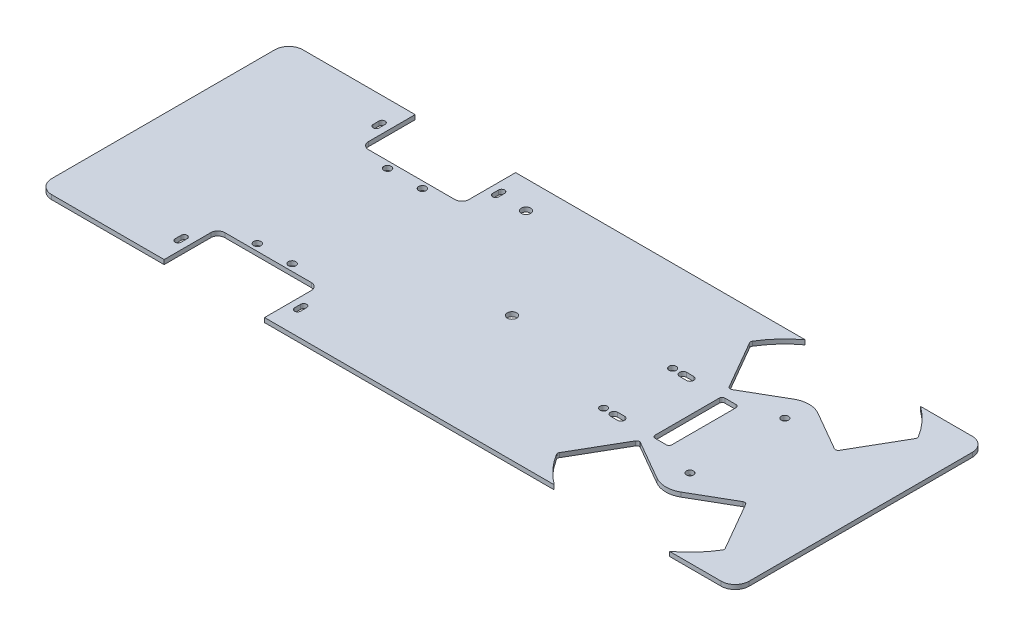
SolidWorks part; units mm, degrees
ref_plane "Front Plane" through (0, 0, 0) normal (0, 0, 1) x (1, 0, 0)
ref_plane "Top Plane" through (0, 0, 0) normal (0, 1, 0) x (1, 0, 0)
ref_plane "Right Plane" through (0, 0, 0) normal (1, 0, 0) x (0, 0, -1)
sketch "Sketch1" plane through (0, 0, 0) normal (0, 1, 0) x (1, 0, 0)
  line L1 (-250, 90) -> (250, 90)
  line L2 (-250, 90) -> (-250, -90)
  line L3 (-250, -90) -> (250, -90)
  line L4 (250, 90) -> (250, -90)
  line L5 (-250, 90) -> (250, -90) construction
  line L6 (-250, -90) -> (250, 90) construction
  point P0 (0, 0)
  dimension "D1" = 180
  dimension "D2" = 500
base flange "Base-Flange1" sketch "Sketch1" thickness 3.175 reverse thickness direction no parameters "D1"=1
fillet "Fillet1" radius 10 4 edges at (250, -1.5875, -90) (250, -1.5875, 90) (-250, -1.5875, -90) (-250, -1.5875, 90)
sketch "Sketch6" plane through (0, 0, 0) normal (0, 1, 0) x (1, 0, 0)
  line L0 (244.3128, -72.65) -> (244.3128, -67.35) construction
  line L1 (241.7206, -72.65) -> (241.7206, -67.35)
  line L2 (246.905, -72.65) -> (246.905, -67.35)
  line L12 (246.905, 67.35) -> (246.905, 72.65)
  line L13 (241.7206, 67.35) -> (241.7206, 72.65)
  line L14 (244.3128, 67.35) -> (244.3128, 72.65) construction
  line L15 (241.7206, -37.65) -> (241.7206, -32.35)
  line L16 (246.905, -37.65) -> (246.905, -32.35)
  line L17 (241.7206, 32.35) -> (241.7206, 37.65)
  line L18 (246.905, 32.35) -> (246.905, 37.65)
  line L19 (241.7206, -2.65) -> (241.7206, 2.65)
  line L20 (246.905, -2.65) -> (246.905, 2.65)
  circle A1 centre (244.3128, -70) radius 2.65 construction
  arc A2 (241.7206, -72.65) -> (246.905, -72.65) centre (244.3128, -72.65) ccw
  arc A3 (246.905, -67.35) -> (241.7206, -67.35) centre (244.3128, -67.35) ccw
  arc A10 (241.7206, 67.35) -> (246.905, 67.35) centre (244.3128, 67.35) ccw
  arc A11 (246.905, 72.65) -> (241.7206, 72.65) centre (244.3128, 72.65) ccw
  arc A12 (241.7206, -37.65) -> (246.905, -37.65) centre (244.3128, -37.65) ccw
  arc A13 (246.905, -32.35) -> (241.7206, -32.35) centre (244.3128, -32.35) ccw
  arc A14 (241.7206, 32.35) -> (246.905, 32.35) centre (244.3128, 32.35) ccw
  arc A15 (246.905, 37.65) -> (241.7206, 37.65) centre (244.3128, 37.65) ccw
  arc A16 (241.7206, -2.65) -> (246.905, -2.65) centre (244.3128, -2.65) ccw
  arc A17 (246.905, 2.65) -> (241.7206, 2.65) centre (244.3128, 2.65) ccw
  point P8 (244.3128, -70)
  point P38 (244.3128, 70)
  point P44 (244.3128, 70)
  dimension "D2" = 2.5922
  dimension "D3" = 5
sketch "Sketch13" plane through (0, 0, 0) normal (0, 1, 0) x (1, 0, 0)
  circle A0 centre (-135.9131, 46.6872) radius 2.65
  circle A1 centre (-135.9131, -46.6872) radius 2.65
  circle A2 centre (-110.9131, -46.6872) radius 2.65
  circle A3 centre (-110.9131, 46.6872) radius 2.65
  dimension "D1" = 5.3
extrude "Cut-Extrude4" cut sketch "Sketch13" against normal through all normal cut yes
sketch "Sketch15" plane through (0, 0, 0) normal (0, 1, 0) x (1, 0, 0)
  line L0 (-240, -90) -> (240, -90) construction
  line L1 (-159.4131, -90) -> (-87.4131, -90)
  line L2 (-159.4131, -90) -> (-159.4131, -56.5)
  line L3 (-154.4131, -51.5) -> (-92.4131, -51.5)
  line L4 (-87.4131, -90) -> (-87.4131, -56.5)
  line L5 (-135.9131, -46.6872) -> (-110.9131, -46.6872) construction
  arc A0 (-92.4131, -51.5) -> (-87.4131, -56.5) centre (-92.4131, -56.5) cw
  arc A1 (-159.4131, -56.5) -> (-154.4131, -51.5) centre (-154.4131, -56.5) cw
  point P10 (-123.4131, -51.5)
  point P11 (-123.4131, -46.6872)
  point P14 (-87.4131, -51.5)
  point P17 (-159.4131, -51.5)
  dimension "D3" = 5
  dimension "D1" = 38.5
  dimension "D2" = 72
extrude "Cut-Extrude5" cut sketch "Sketch15" against normal through all normal cut yes
mirror "Mirror1" about plane through (0, 0, 0) normal (0, 0, 1) of "Cut-Extrude5"
sketch "Sketch16" plane through (0, 0, 0) normal (0, 1, 0) x (1, 0, 0)
  line L0 (-80.5767, 68.835) -> (-80.5767, 73.135) construction
  line L1 (-82.7267, 68.835) -> (-82.7267, 73.135)
  line L2 (-78.4267, 68.835) -> (-78.4267, 73.135)
  line L3 (-123.4131, 51.5) -> (-123.4131, 90) construction
  line L4 (-92.4131, 51.5) -> (-154.4131, 51.5) construction
  line L5 (-166.2496, 68.835) -> (-166.2496, 73.135) construction
  line L6 (-164.0996, 68.835) -> (-164.0996, 73.135)
  line L7 (-168.3996, 68.835) -> (-168.3996, 73.135)
  circle A0 centre (-80.5767, 70.985) radius 2.15 construction
  arc A1 (-82.7267, 68.835) -> (-78.4267, 68.835) centre (-80.5767, 68.835) ccw
  arc A2 (-78.4267, 73.135) -> (-82.7267, 73.135) centre (-80.5767, 73.135) ccw
  arc A3 (-164.0996, 68.835) -> (-168.3996, 68.835) centre (-166.2496, 68.835) cw
  arc A4 (-168.3996, 73.135) -> (-164.0996, 73.135) centre (-166.2496, 73.135) cw
  point P6 (-80.5767, 70.985)
  point P18 (-166.2496, 70.985)
  dimension "D1" = 2.15
extrude "Cut-Extrude6" cut sketch "Sketch16" against normal through all normal cut yes
sketch "Sketch21" plane through (0, 0, 0) normal (0, 1, 0) x (1, 0, 0)
  line L3 (102.8888, -24.75) -> (97.8888, -24.75) construction
  line L4 (102.8888, -27.3) -> (97.8888, -27.3)
  line L5 (102.8888, -22.2) -> (97.8888, -22.2)
  line L6 (161.6118, -34) -> (161.6118, -51.35) construction
  line L7 (122.1455, -33.5576) -> (102.1455, -68.1986)
  line L8 (161.728, -102.5986) -> (181.728, -67.9576) construction
  line L9 (180.996, -65.2255) -> (124.8775, -32.8255) construction
  line L10 (152.9368, -49.0255) -> (124.8775, -32.8255) construction
  line L11 (161.6118, -34) -> (152.9368, -49.0255) construction
  line L12 (102.8775, -70.9307) -> (158.996, -103.3307) construction
  line L13 (164.2275, -103.3307) -> (220.346, -70.9307) construction
  line L14 (221.078, -68.1986) -> (201.078, -33.5576)
  line L15 (198.346, -32.8255) -> (142.2275, -65.2255) construction
  line L16 (141.4955, -67.9576) -> (161.4955, -102.5986) construction
  line L17 (161.6118, -34) -> (170.2868, -49.0255) construction
  line L18 (170.2868, -49.0255) -> (142.2275, -65.2255) construction
  line L19 (198.346, -32.8255) -> (170.2868, -49.0255)
  line L20 (152.9368, -49.0255) -> (124.8775, -32.8255)
  circle A4 centre (90.3888, -24.75) radius 2.55
  arc A5 (102.8888, -27.3) -> (102.8888, -22.2) centre (102.8888, -24.75) ccw
  arc A6 (97.8888, -22.2) -> (97.8888, -27.3) centre (97.8888, -24.75) ccw
  circle A7 centre (161.6118, -34) radius 17.35 construction
  arc A8 (102.1699, -70.2397) -> (221.0537, -70.2397) centre (161.6118, -34) ccw
  arc A9 (158.996, -103.3307) -> (161.728, -102.5986) centre (159.996, -101.5986) ccw construction
  arc A10 (102.1455, -68.1986) -> (102.1699, -70.2397) centre (103.8775, -69.1986) ccw
  arc A11 (181.728, -67.9576) -> (180.996, -65.2255) centre (179.996, -66.9576) ccw construction
  arc A12 (124.8775, -32.8255) -> (122.1455, -33.5576) centre (123.8775, -34.5576) ccw
  arc A13 (221.0537, -70.2397) -> (221.078, -68.1986) centre (219.346, -69.1986) ccw
  arc A14 (201.078, -33.5576) -> (198.346, -32.8255) centre (199.346, -34.5576) ccw
  arc A15 (161.4955, -102.5986) -> (164.2275, -103.3307) centre (163.2275, -101.5986) ccw construction
  arc A16 (142.2275, -65.2255) -> (141.4955, -67.9576) centre (143.2275, -66.9576) ccw construction
  arc A17 (170.2868, -49.0255) -> (152.9368, -49.0255) centre (161.6118, -34) cw
  arc A18 (221.078, -68.1986) -> (220.346, -70.9307) centre (219.346, -69.1986) cw construction
  circle A19 centre (161.6118, -34) radius 2.55
  point P0 (161.6118, -34)
  point P1 (161.6118, -34)
  point P4 (90.3888, -24.75)
  point P13 (100.3888, -24.75)
  dimension "D2" = 5.1
  dimension "D5" = 5.1
  dimension "D6" = 2.55
  dimension "D8" = 2
  dimension "D14" = 34.7
  dimension "D7" = 5
  dimension "D9" = 40
  dimension "D10" = 30
  dimension "D11" = 60
  dimension "D12" = 32.4
  dimension "D13" = 32.4
extrude "Cut-Extrude7" cut sketch "Sketch21" against normal blind 10 normal cut yes
mirror "Mirror2" about plane through (0, 0, 0) normal (0, 0, 1) of "Cut-Extrude7"
mirror "Mirror3" about plane through (0, 0, 0) normal (0, 0, 1) of "Cut-Extrude6"
sketch "Sketch25" plane through (0, 0, 0) normal (0, 1, 0) x (1, 0, 0)
  line L1 (127.6088, 25) -> (135.6088, 25)
  line L2 (125.6088, 23) -> (125.6088, -23)
  line L3 (127.6088, -25) -> (135.6088, -25)
  line L4 (137.6088, 23) -> (137.6088, -23)
  arc A0 (135.6088, -25) -> (137.6088, -23) centre (135.6088, -23) ccw
  arc A1 (125.6088, -23) -> (127.6088, -25) centre (127.6088, -23) ccw
  arc A2 (135.6088, 25) -> (137.6088, 23) centre (135.6088, 23) cw
  arc A3 (127.6088, 25) -> (125.6088, 23) centre (127.6088, 23) ccw
  point P0 (90.3888, 24.75)
  point P6 (137.6088, 0)
  point P12 (125.6088, -25)
  point P15 (137.6088, 25)
  point P18 (125.6088, 25)
  dimension "D4" = 2
  dimension "D1" = 35.22
  dimension "D2" = 12
  dimension "D3" = 50
extrude "Cut-Extrude8" cut sketch "Sketch25" against normal through all normal cut yes
sketch "Sketch26" plane through (0, 0, 0) normal (0, 1, 0) x (1, 0, 0)
  circle A0 centre (0, 0) radius 3.35
  dimension "D1" = 6.7
extrude "Cut-Extrude9" cut sketch "Sketch26" against normal through all normal cut yes
sketch "Sketch27" plane through (0, 0, 0) normal (0, 1, 0) x (1, 0, 0)
  circle A0 centre (-60, 70) radius 3.35
  dimension "D1" = 6.7
  dimension "D2" = 60
  dimension "D3" = 70
extrude "Cut-Extrude10" cut sketch "Sketch27" against normal through all normal cut yes
sketch "Bend-Lines1" [suppressed] plane through (0, 0, 0) normal (0, 1, 0) x (1, 0, 0)
sketch "Bounding-Box1" [suppressed] plane through (0, 0, 0) normal (0, 1, 0) x (1, 0, 0)
sheet metal parameters "Sheet-Metal1" thickness 3.175 parameters "D1"=1
flat pattern "Flat-Pattern1" [suppressed]
sketch "Bend-Lines2" plane through (0, 0, 0) normal (0, 1, 0) x (1, 0, 0)
sketch3d "Bounding-Box2" [suppressed]
  line L0 (-250, -90, 0) -> (250, -90, 0) construction
  line L1 (-250, 90, 0) -> (250, 90, 0) construction
  line L2 (-250, -90, 0) -> (-250, 90, 0) construction
  line L3 (250, -90, 0) -> (250, 90, 0) construction
sheet metal parameters "Sheet-Metal5" thickness 3.175 parameters "D1"=1
flat pattern "Flat-Pattern1"
sketch "Bend-Lines2" plane through (0, 0, 0) normal (0, 1, 0) x (1, 0, 0)
sketch3d "Bounding-Box2" [suppressed]
  line L0 (-250, -90, 0) -> (250, -90, 0) construction
  line L1 (-250, 90, 0) -> (250, 90, 0) construction
  line L2 (-250, -90, 0) -> (-250, 90, 0) construction
  line L3 (250, -90, 0) -> (250, 90, 0) construction
sheet metal parameters "Sheet-Metal6" thickness 3.175 parameters "D1"=1
flat pattern "Flat-Pattern1"
sketch "Bend-Lines2" plane through (0, 0, 0) normal (0, 1, 0) x (1, 0, 0)
sketch3d "Bounding-Box2" [suppressed]
  line L0 (-250, -90, 0) -> (250, -90, 0) construction
  line L1 (-250, 90, 0) -> (250, 90, 0) construction
  line L2 (-250, -90, 0) -> (-250, 90, 0) construction
  line L3 (250, -90, 0) -> (250, 90, 0) construction
sheet metal parameters "Sheet-Metal7" thickness 3.175 parameters "D1"=1
flat pattern "Flat-Pattern1"
sketch "Bend-Lines2" plane through (0, 0, 0) normal (0, 1, 0) x (1, 0, 0)
sketch3d "Bounding-Box2" [suppressed]
  line L0 (-250, -90, 0) -> (250, -90, 0) construction
  line L1 (-250, 90, 0) -> (250, 90, 0) construction
  line L2 (-250, -90, 0) -> (-250, 90, 0) construction
  line L3 (250, -90, 0) -> (250, 90, 0) construction
sheet metal parameters "Sheet-Metal8" thickness 3.175 parameters "D1"=1
flat pattern "Flat-Pattern1"
sketch "Bend-Lines2" plane through (0, 0, 0) normal (0, 1, 0) x (1, 0, 0)
sketch3d "Bounding-Box2" [suppressed]
  line L0 (-250, -90, 0) -> (250, -90, 0) construction
  line L1 (-250, 90, 0) -> (250, 90, 0) construction
  line L2 (-250, -90, 0) -> (-250, 90, 0) construction
  line L3 (250, -90, 0) -> (250, 90, 0) construction
sheet metal parameters "Sheet-Metal9" thickness 3.175 parameters "D1"=1
flat pattern "Flat-Pattern1"
sketch "Bend-Lines2" plane through (0, 0, 0) normal (0, 1, 0) x (1, 0, 0)
sketch3d "Bounding-Box2" [suppressed]
  line L0 (-250, -90, 0) -> (250, -90, 0) construction
  line L1 (-250, 90, 0) -> (250, 90, 0) construction
  line L2 (-250, -90, 0) -> (-250, 90, 0) construction
  line L3 (250, -90, 0) -> (250, 90, 0) construction
sheet metal parameters "Sheet-Metal10" thickness 3.175 parameters "D1"=1
flat pattern "Flat-Pattern1"
sketch "Bend-Lines2" plane through (0, 0, 0) normal (0, 1, 0) x (1, 0, 0)
sketch3d "Bounding-Box2" [suppressed]
  line L0 (-250, -90, 0) -> (250, -90, 0) construction
  line L1 (-250, 90, 0) -> (250, 90, 0) construction
  line L2 (-250, -90, 0) -> (-250, 90, 0) construction
  line L3 (250, -90, 0) -> (250, 90, 0) construction
sheet metal parameters "Sheet-Metal11" thickness 3.175 parameters "D1"=1
flat pattern "Flat-Pattern1"
sketch "Bend-Lines2" plane through (0, 0, 0) normal (0, 1, 0) x (1, 0, 0)
sketch3d "Bounding-Box2" [suppressed]
  line L0 (-250, -90, 0) -> (250, -90, 0) construction
  line L1 (-250, 90, 0) -> (250, 90, 0) construction
  line L2 (-250, -90, 0) -> (-250, 90, 0) construction
  line L3 (250, -90, 0) -> (250, 90, 0) construction
sheet metal parameters "Sheet-Metal12" thickness 3.175 parameters "D1"=1
flat pattern "Flat-Pattern1"
sketch "Bend-Lines2" plane through (0, 0, 0) normal (0, 1, 0) x (1, 0, 0)
sketch3d "Bounding-Box2" [suppressed]
  line L0 (-250, -90, 0) -> (250, -90, 0) construction
  line L1 (-250, 90, 0) -> (250, 90, 0) construction
  line L2 (-250, -90, 0) -> (-250, 90, 0) construction
  line L3 (250, -90, 0) -> (250, 90, 0) construction
sheet metal parameters "Sheet-Metal14" thickness 3.175 parameters "D1"=1
flat pattern "Flat-Pattern1"
sketch "Bend-Lines2" plane through (0, 0, 0) normal (0, 1, 0) x (1, 0, 0)
sketch3d "Bounding-Box2" [suppressed]
  line L0 (-250, -90, 0) -> (250, -90, 0) construction
  line L1 (-250, 90, 0) -> (250, 90, 0) construction
  line L2 (-250, -90, 0) -> (-250, 90, 0) construction
  line L3 (250, -90, 0) -> (250, 90, 0) construction
sheet metal parameters "Sheet-Metal15" thickness 3.175 parameters "D1"=1
flat pattern "Flat-Pattern1"
sketch "Bend-Lines2" plane through (0, 0, 0) normal (0, 1, 0) x (1, 0, 0)
sketch3d "Bounding-Box2" [suppressed]
  line L0 (-250, -90, 0) -> (250, -90, 0) construction
  line L1 (-250, 90, 0) -> (250, 90, 0) construction
  line L2 (-250, -90, 0) -> (-250, 90, 0) construction
  line L3 (250, -90, 0) -> (250, 90, 0) construction
